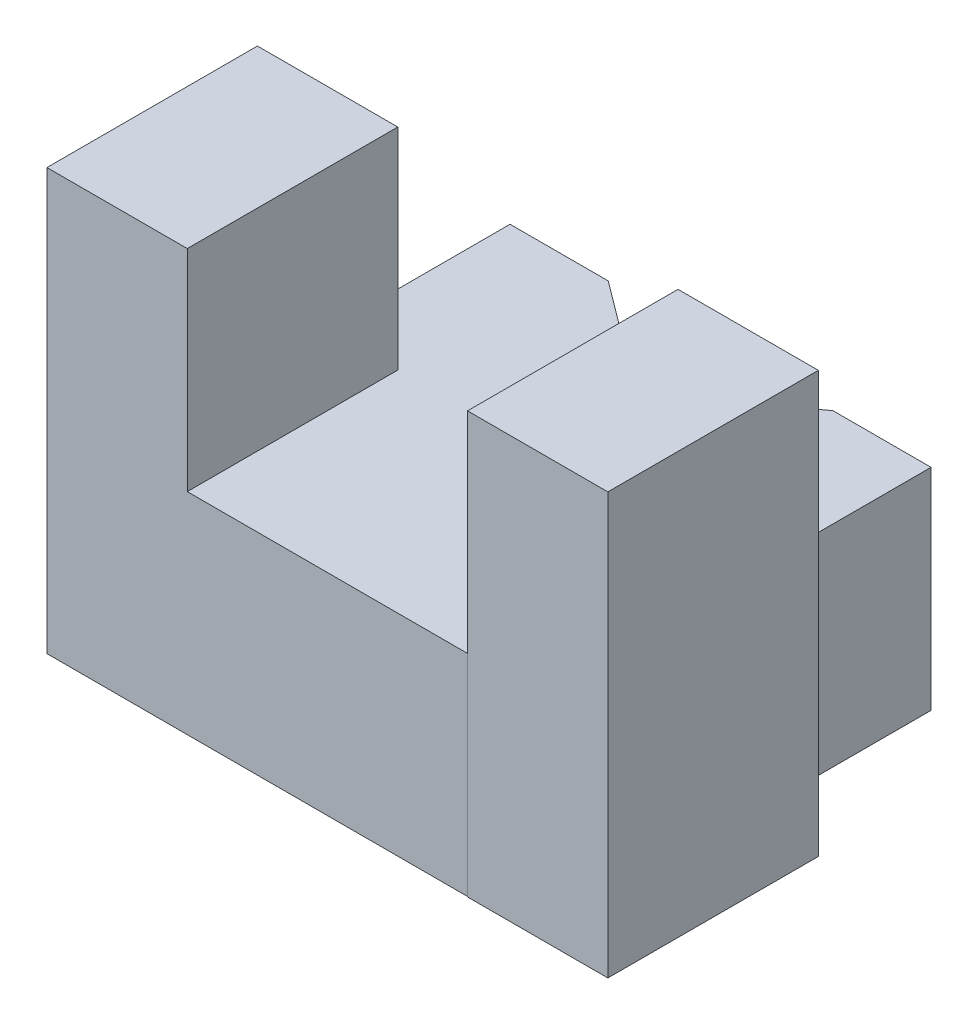
SolidWorks part; units mm, degrees
ref_plane "前视基准面" through (0, 0, 0) normal (0, 0, 1) x (1, 0, 0)
ref_plane "上视基准面" through (0, 0, 0) normal (0, 1, 0) x (1, 0, 0)
ref_plane "右视基准面" through (0, 0, 0) normal (1, 0, 0) x (0, 0, -1)
sketch "草图1" plane through (0, 0, 0) normal (0, 1, 0) x (1, 0, 0)
  line L0 (15, -6) -> (15, -28) construction
  line L1 (0, 0) -> (7, 0)
  line L2 (0, 0) -> (0, -28)
  line L3 (0, -28) -> (30, -28)
  line L4 (30, 0) -> (30, -28)
  line L5 (15, -6) -> (23, 0)
  line L6 (15, -6) -> (7, 0)
  line L7 (23, 0) -> (30, 0)
  dimension "D1" = 30
  dimension "D2" = 28
  dimension "D3" = 28
  dimension "D4" = 6
  dimension "D6" = 8
extrude "凸台-拉伸1" add sketch "草图1" along normal blind 15
sketch "草图2" plane through (0, 15, 0) normal (0, 1, 0) x (1, 0, 0)
  line L0 (0, -28) -> (30, -28) construction
  line L1 (25, -13.0312) -> (35, -13.0312)
  line L2 (25, -13.0312) -> (25, -28.0312)
  line L3 (25, -28.0312) -> (35, -28.0312)
  line L4 (35, -13.0312) -> (35, -28.0312)
  line L6 (-5, -13) -> (5, -13)
  line L7 (-5, -13) -> (-5, -28)
  line L8 (-5, -28) -> (5, -28)
  line L9 (5, -13) -> (5, -28)
  point P4 (15, -28)
  dimension "D1" = 15
  dimension "D2" = 10
  dimension "D3" = 5
  dimension "D4" = 15
  dimension "D5" = 10
  dimension "D6" = 5
  dimension "D7" = 20
extrude "凸台-拉伸7" add sketch "草图2" along normal blind 15 and the other way blind 15
ref_plane "基准面1" through (5, 15, 28) normal (0, 0, -1) x (-1, 0, 0)
